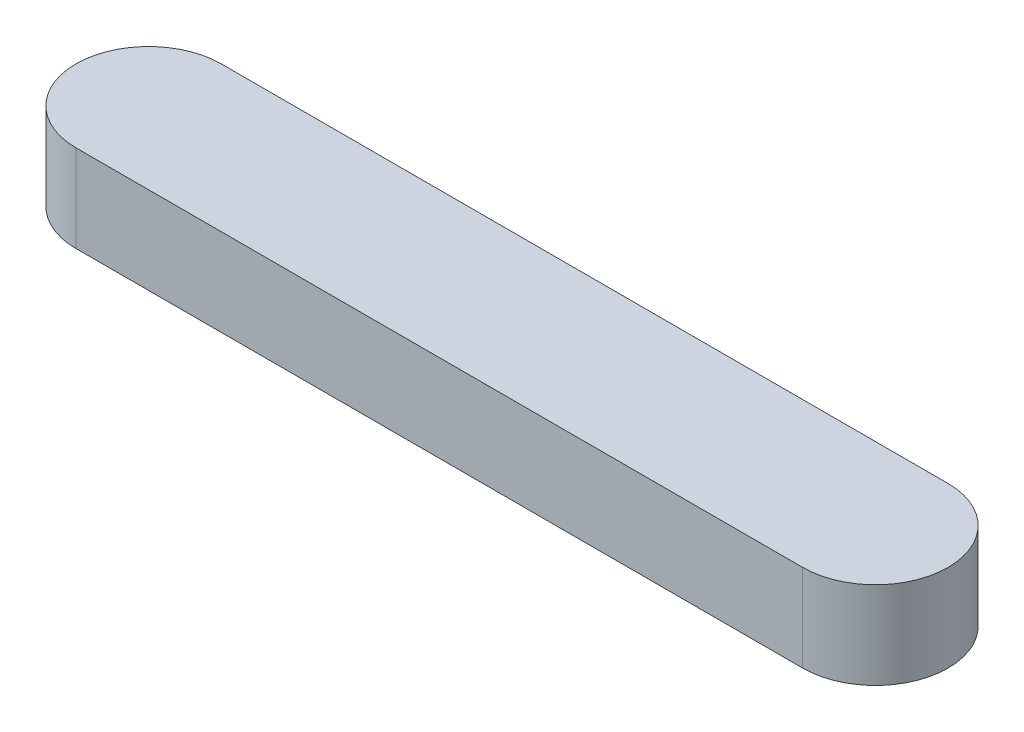
SolidWorks part; units mm, degrees
ref_plane "Front" through (0, 0, 0) normal (0, 0, 1) x (1, 0, 0)
ref_plane "Top" through (0, 0, 0) normal (0, 1, 0) x (1, 0, 0)
ref_plane "Right" through (0, 0, 0) normal (1, 0, 0) x (0, 0, -1)
sketch "Esquisse1" plane through (0, 0, 0) normal (0, 1, 0) x (1, 0, 0)
  line L0 (50, 0) -> (-50, 0) construction
  line L1 (50, -10) -> (-50, -10)
  line L2 (50, 10) -> (-50, 10)
  arc A0 (50, -10) -> (50, 10) centre (50, 0) ccw
  arc A1 (-50, 10) -> (-50, -10) centre (-50, 0) ccw
  point P2 (0, 0)
  dimension "D2" = 10
  dimension "D1" = 100
extrude "Boss.-Extru.1" add sketch "Esquisse1" along normal blind 12
